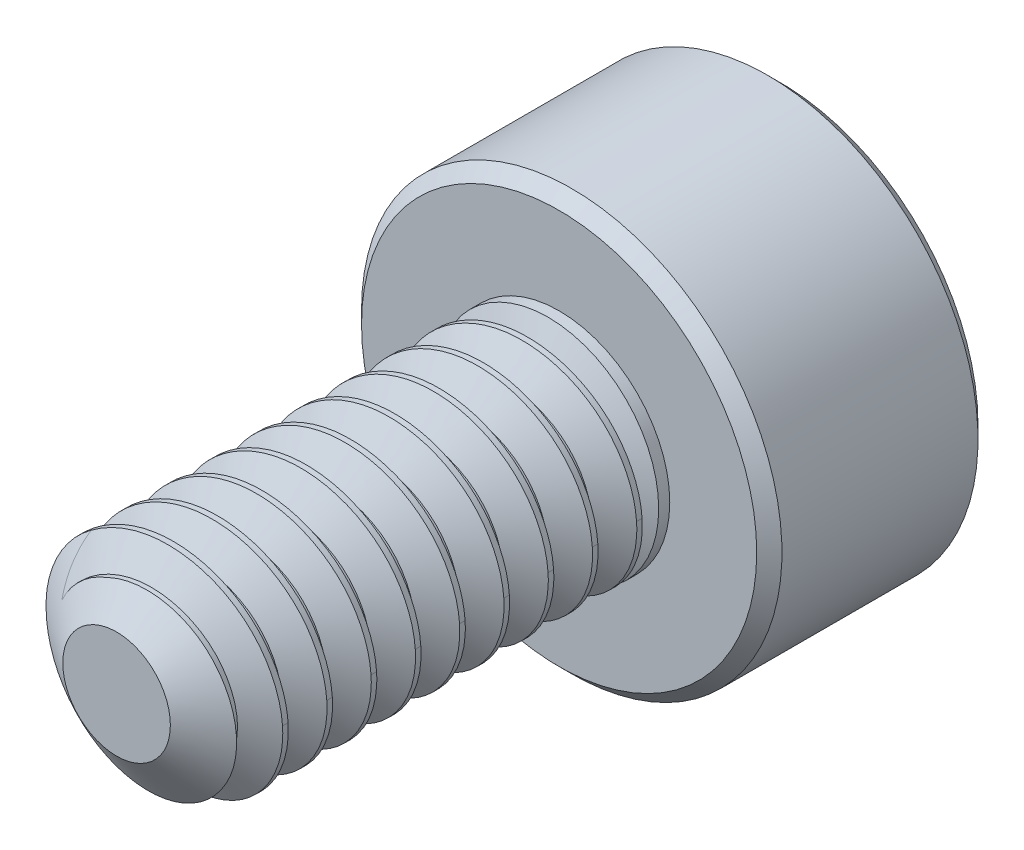
SolidWorks part; units mm, degrees
ref_plane "Front Plane" through (0, 0, 0) normal (0, 0, 1) x (1, 0, 0)
ref_plane "Top Plane" through (0, 0, 0) normal (0, 1, 0) x (1, 0, 0)
ref_plane "Right Plane" through (0, 0, 0) normal (1, 0, 0) x (0, 0, -1)
sketch "Sketch1" plane through (0, 0, 0) normal (0, 0, 1) x (1, 0, 0)
  circle A0 centre (0, 0) radius 1
  dimension "OD" = 2
extrude "Extrude1" add sketch "Sketch1" against normal blind 4
sketch "Sketch2" plane through (0, 0, 0) normal (0, 0, 1) x (1, 0, 0)
  circle A0 centre (0, 0) radius 1 construction
  circle A1 centre (0, 0) radius 1
curve "Helix/Spiral1" pitch 0.4 height 4.4 radius 1 centre (0, 0, 0) axis (0, 0, -1) start towards (0, 1, 0) parameters "pitch"=0.4
sketch "Sketch3" plane through (0, 0, 0) normal (1, 0, 0) x (0, 0, -1)
  line L0 (-0.35, 1) -> (-0.2, 0.7402)
  line L1 (-0.2, 0.7402) -> (-0.15, 0.7402)
  line L2 (-0.15, 0.7402) -> (0, 1)
  line L3 (-0.35, 1) -> (0, 1)
  line L4 (-0.175, 1) -> (-0.175, 0.7402) construction
  line L5 (-0.275, 0.8701) -> (-0.075, 0.8701) construction
  line L6 (0, 1) -> (0, -1) construction
  line L7 (0, -1) -> (4, -1) construction
  point P11 (1.8, -1)
  dimension "D1" = 0.05
  dimension "D2" = 0.2
  dimension "D3" = 60
  dimension "D4" = 1.8
sweep "Cut-Sweep1" cut profiles "Sketch3" path "Helix/Spiral1" align with end faces yes
sketch "Sketch4" plane through (0, 0, 0) normal (1, 0, 0) x (0, 0, -1)
  line L0 (0.3598, 1) -> (0, 0.4862)
  line L1 (0, 0.4862) -> (0, 1)
  line L2 (0.3598, 1) -> (0, 1)
  line L3 (-0.35, 1) -> (0, 1) construction
  line L4 (0, 0) -> (7.0209, 0) construction
  dimension "D1" = 55
  dimension "D2" = 0.254
revolve "Cut-Revolve1" cut sketch "Sketch4" angle 360 about L4
sketch "Sketch5" plane through (0, 0, 0) normal (1, 0, 0) x (0, 0, -1)
  line L0 (4, -0.7473) -> (4, 0.7135) construction
  line L1 (4, 1) -> (0.1203, 1)
  line L2 (4, 1) -> (4, 0)
  line L3 (4, 0) -> (0.0001, 0)
  line L4 (0.0001, 0.6698) -> (0.0001, 0)
  line L5 (0.1203, 1) -> (0.0001, 0.6698)
  line L6 (0, 0) -> (9.9695, 0) construction
  point P3 (0.0001, 1)
  point P10 (0.0001, 1)
  dimension "D1" = 0.3302
  dimension "Thread min" = 0.0001
  dimension "D3" = 20
revolve "partially thread" [suppressed] add sketch "Sketch5" angle 360 about L6
sketch "Sketch6" plane through (0, 0, -4) normal (0, 0, -1) x (-1, 0, 0)
  circle A0 centre (0, 0) radius 1.9
  dimension "head dia" = 3.8
extrude "Extrude2" add sketch "Sketch6" along normal blind 2
sketch "Sketch7" plane through (0, 0, -6) normal (0, 0, -1) x (-1, 0, 0)
  line L1 (0, 0.866) -> (-0.75, 0.433)
  line L2 (-0.75, 0.433) -> (-0.75, -0.433)
  line L3 (-0.75, -0.433) -> (0, -0.866)
  line L4 (0, -0.866) -> (0.75, -0.433)
  line L5 (0.75, -0.433) -> (0.75, 0.433)
  line L6 (0.75, 0.433) -> (0, 0.866)
  circle A0 centre (0, 0) radius 0.75 construction
  dimension "hex dia" = 1.5
extrude "Cut-Extrude1" cut sketch "Sketch7" against normal blind 1.125
sketch "Sketch8" plane through (0, 0, -6) normal (0, 0, -1) x (-1, 0, 0)
  circle A0 centre (0, 0) radius 0.866
extrude "Cut-Extrude2" cut sketch "Sketch8" against normal through all draft 45
chamfer "Chamfer1" distance 0.114 angle 45 2 edges at (-1.9, 0, -6) (-1.9, 0, -4)
sketch "Sketch9" plane through (0, 0, 0) normal (1, 0, 0) x (0, 0, -1)
  line L0 (0, 1) -> (0, -1) construction
  line L1 (2.2, 1) -> (2.2, -1) construction
  dimension "D1" = 2.2
sketch "Sketch10" plane through (0, 0, 0) normal (1, 0, 0) x (0, 0, -1)
  line L0 (4, 1) -> (4, 0)
  line L1 (4, 1) -> (3.9, 1)
  line L2 (3.9, 1) -> (3.4858, 0)
  line L3 (4, 0) -> (3.4858, 0)
  line L4 (4, 1.786) -> (4, -1.786) construction
  dimension "D1" = 22.5
  dimension "D2" = 0.1
revolve "Revolve1" add sketch "Sketch10" angle 360 about L3
equation "\"D3@Helix/Spiral1\" = \"screw length@Extrude1\"+\"pitch@Helix/Spiral1\""
equation "\"D1@Sketch3\" = \"pitch@Helix/Spiral1\"*.125"
equation "\"D2@Sketch3\" = \"pitch@Helix/Spiral1\"*.5"
equation "\"D1@Cut-Extrude1\" = \"hex dia@Sketch7\"*.75"
equation "\"D1@Chamfer1\" = \"head dia@Sketch6\"*.03"
equation "\"D1@Sketch9\" = \"pitch@Helix/Spiral1\"*5.5"
equation "\"D2@Sketch10\" = \"pitch@Helix/Spiral1\"*.25"
equation "\"D4@Sketch3\" = \"pitch@Helix/Spiral1\"*4.50"
